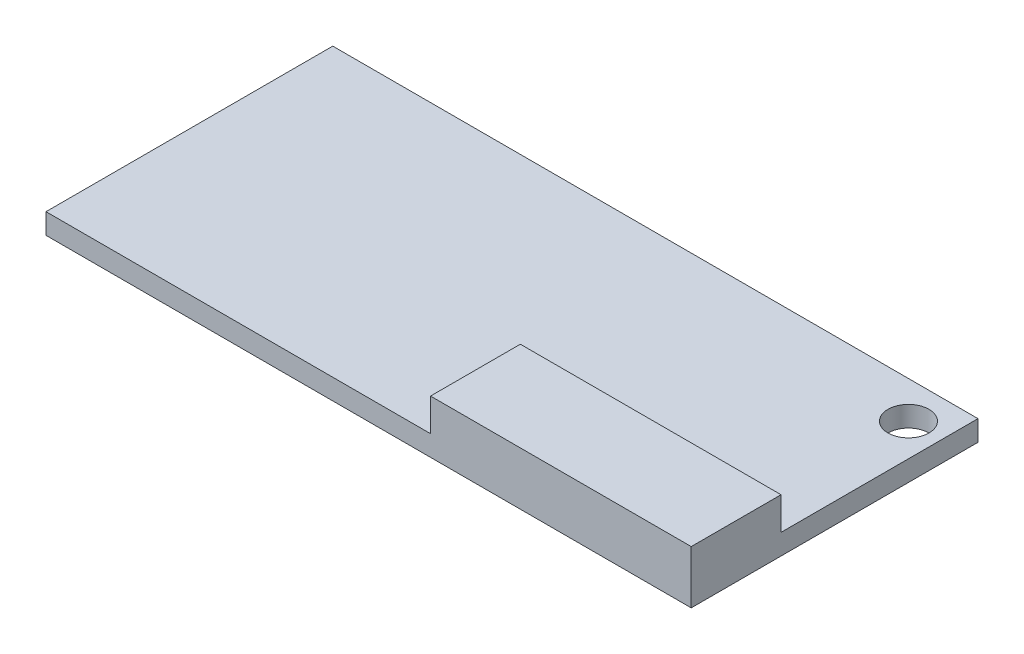
SolidWorks part; units mm, degrees
ref_plane "Front Plane" through (0, 0, 0) normal (0, 0, 1) x (1, 0, 0)
ref_plane "Top Plane" through (0, 0, 0) normal (0, 1, 0) x (1, 0, 0)
ref_plane "Right Plane" through (0, 0, 0) normal (1, 0, 0) x (0, 0, -1)
sketch "Sketch1" plane through (0, 0, 0) normal (0, 1, 0) x (1, 0, 0)
  line L1 (-25.146, -11.176) -> (25.146, -11.176)
  line L2 (-25.146, -11.176) -> (-25.146, 11.176)
  line L3 (-25.146, 11.176) -> (25.146, 11.176)
  line L4 (25.146, -11.176) -> (25.146, 11.176)
  line L5 (-25.146, -11.176) -> (25.146, 11.176) construction
  line L6 (-25.146, 11.176) -> (25.146, -11.176) construction
  circle A0 centre (22.606, 8.2962) radius 1.6
  point P0 (0, 0)
  dimension "D3" = 3.2
  dimension "D1" = 50.292
  dimension "D2" = 22.352
  dimension "D4" = 47.752
extrude "Boss-Extrude1" add sketch "Sketch1" along normal blind 1.6
sketch "Sketch2" plane through (0, 1.6, 0) normal (0, 1, 0) x (1, 0, 0)
  line L1 (25.146, -11.176) -> (4.826, -11.176)
  line L2 (25.146, -11.176) -> (25.146, -4.176)
  line L3 (25.146, -4.176) -> (4.826, -4.176)
  line L4 (4.826, -11.176) -> (4.826, -4.176)
  dimension "D1" = 7
  dimension "D2" = 20.32
extrude "Boss-Extrude2" add sketch "Sketch2" along normal blind 2.54
sketch "Sketch3" plane through (0, 0, 0) normal (0, -1, 0) x (1, 0, 0)
  line L1 (-25.146, -11.176) -> (18.034, -11.176)
  line L2 (-25.146, -11.176) -> (-25.146, -3.556)
  line L3 (-25.146, -3.556) -> (18.034, -3.556)
  line L4 (18.034, -11.176) -> (18.034, -3.556)
  dimension "D1" = 7.62
  dimension "D2" = 43.18
extrude "Boss-Extrude3" add sketch "Sketch3" along normal blind 2.54
